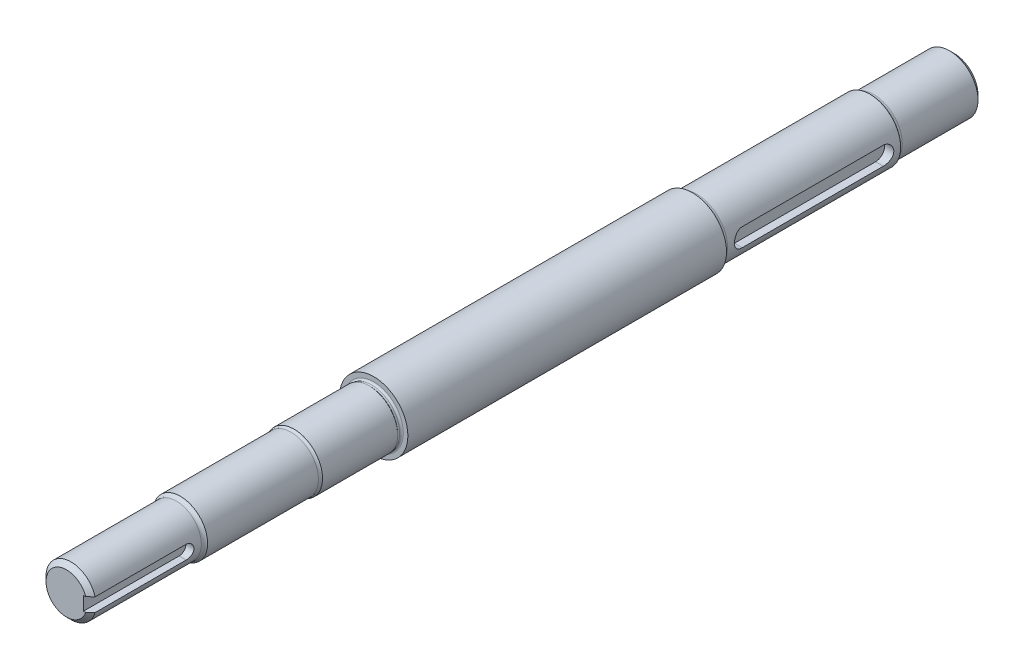
SolidWorks part; units mm, degrees
ref_plane "前视基准面" through (0, 0, 0) normal (0, 0, 1) x (1, 0, 0)
ref_plane "上视基准面" through (0, 0, 0) normal (0, 1, 0) x (1, 0, 0)
ref_plane "右视基准面" through (0, 0, 0) normal (1, 0, 0) x (0, 0, -1)
sketch "草图1" plane through (0, 0, 0) normal (1, 0, 0) x (0, 0, -1)
  line L0 (-55.0258, 0) -> (2696.263, 0) construction
  line L1 (-275, 0) -> (-275, 11)
  line L2 (-275, 11) -> (-225, 11)
  line L3 (-225, 11) -> (-225, 12)
  line L4 (-225, 12) -> (-175, 12)
  line L5 (-175, 12) -> (-175, 12.5)
  line L6 (-175, 12.5) -> (-142, 12.5)
  line L7 (-142, 12.5) -> (-141.7, 12.2)
  line L8 (-141.7, 12.2) -> (-140.8, 12.2)
  line L9 (-140, 13) -> (-140, 15)
  line L10 (-140, 15) -> (0, 15)
  line L11 (0, 15) -> (0, 13.5)
  line L12 (0, 13.5) -> (78, 13.5)
  line L13 (78, 13.5) -> (78, 12.5)
  line L14 (78, 12.5) -> (115, 12.5)
  line L15 (115, 12.5) -> (115, 0)
  line L16 (-275, 0) -> (115, 0)
  arc A0 (-140, 13) -> (-140.8, 12.2) centre (-140.8, 13) cw
  point P21 (-187.6693, 11)
  point P22 (-187.6693, 0)
  dimension "D4" = 0.8
  dimension "D1" = 0.3
  dimension "D2" = 135
  dimension "D3" = 2
  dimension "D5" = 11
  dimension "D6" = 12
  dimension "D7" = 12.5
  dimension "D8" = 15
  dimension "D9" = 12.5
  dimension "D10" = 13.5
  dimension "D11" = 50
  dimension "D12" = 50
  dimension "D13" = 35
  dimension "D14" = 140
  dimension "D15" = 37
  dimension "D16" = 78
revolve "旋转1" add sketch "草图1" angle 360 about L0
fillet "圆角1" radius 2 4 edges at (12.5, 0, -78) (13.5, 0, 0) (12, 0, 175) (11, 0, 225)
chamfer "倒角1" distance 2 angle 45 2 edges at (11, 0, 275) (12.5, 0, -115)
ref_plane "基准面1" through (7.5, 0, 0) normal (1, 0, 0) x (0, 0, -1)
sketch "草图2" plane through (7.5, 0, 0) normal (1, 0, 0) x (0, 0, -1)
  line L0 (-275, 0) -> (-233, 0) construction
  line L1 (-275, 9) -> (-275, -9) construction
  line L2 (-275, 3) -> (-233, 3)
  line L3 (-275, -3) -> (-233, -3)
  line L4 (-275, 3) -> (-275, -3)
  arc A1 (-233, -3) -> (-233, 3) centre (-233, 0) ccw
  point P5 (-254, 0)
extrude "切除-拉伸1" cut sketch "草图2" along normal blind 17
ref_plane "基准面2" through (9.5, 0, 0) normal (1, 0, 0) x (0, 0, -1)
sketch "草图3" plane through (9.5, 0, 0) normal (1, 0, 0) x (0, 0, -1)
  line L0 (9, 0) -> (71, 0) construction
  line L1 (9, 4) -> (71, 4)
  line L2 (9, -4) -> (71, -4)
  arc A0 (9, 4) -> (9, -4) centre (9, 0) ccw
  arc A1 (71, -4) -> (71, 4) centre (71, 0) ccw
  point P3 (40, 0)
  point P8 (5, 0)
  dimension "D1" = 5
extrude "切除-拉伸2" cut sketch "草图3" along normal blind 51
